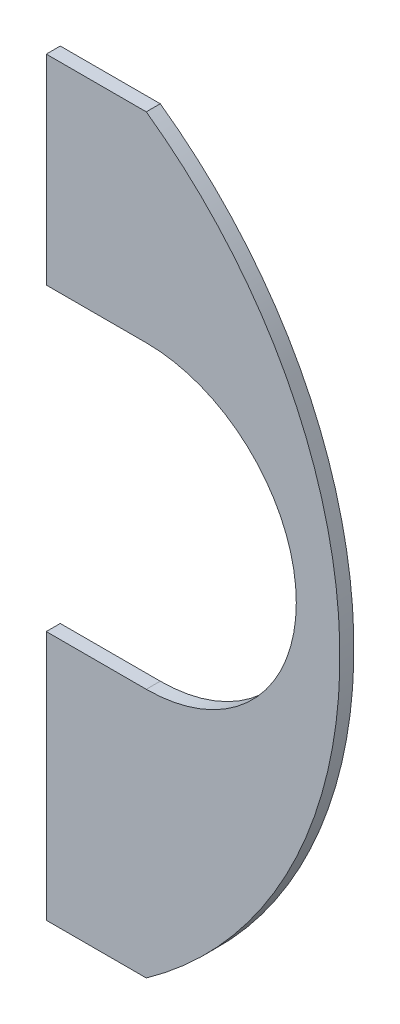
SolidWorks part; units mm, degrees
ref_plane "Front Plane" through (0, 0, 0) normal (0, 0, 1) x (1, 0, 0)
ref_plane "Top Plane" through (0, 0, 0) normal (0, 1, 0) x (1, 0, 0)
ref_plane "Right Plane" through (0, 0, 0) normal (1, 0, 0) x (0, 0, -1)
sketch "Sketch1" plane through (0, 0, 0) normal (0, 0, 1) x (1, 0, 0)
  line L1 (0, 0) -> (5, 0)
  line L2 (0, 0) -> (0, 12.5)
  line L3 (0, 12.5) -> (5, 12.5)
  line L4 (5, 0) -> (5, 12.5) construction
  line L5 (0, 27.5) -> (5, 27.5)
  line L6 (0, 27.5) -> (0, 37.5)
  line L7 (0, 37.5) -> (5, 37.5)
  line L8 (5, 27.5) -> (5, 37.5) construction
  arc A0 (5, 37.5) -> (5, 0) centre (-8.3206, 18.75) cw
  arc A1 (5, 27.5) -> (5, 12.5) centre (5, 20) cw
  dimension "D5" = 23
  dimension "D1" = 12.5
  dimension "D2" = 10
  dimension "D3" = 15
  dimension "D4" = 5
extrude "Boss-Extrude1" add sketch "Sketch1" along normal blind 0.7
